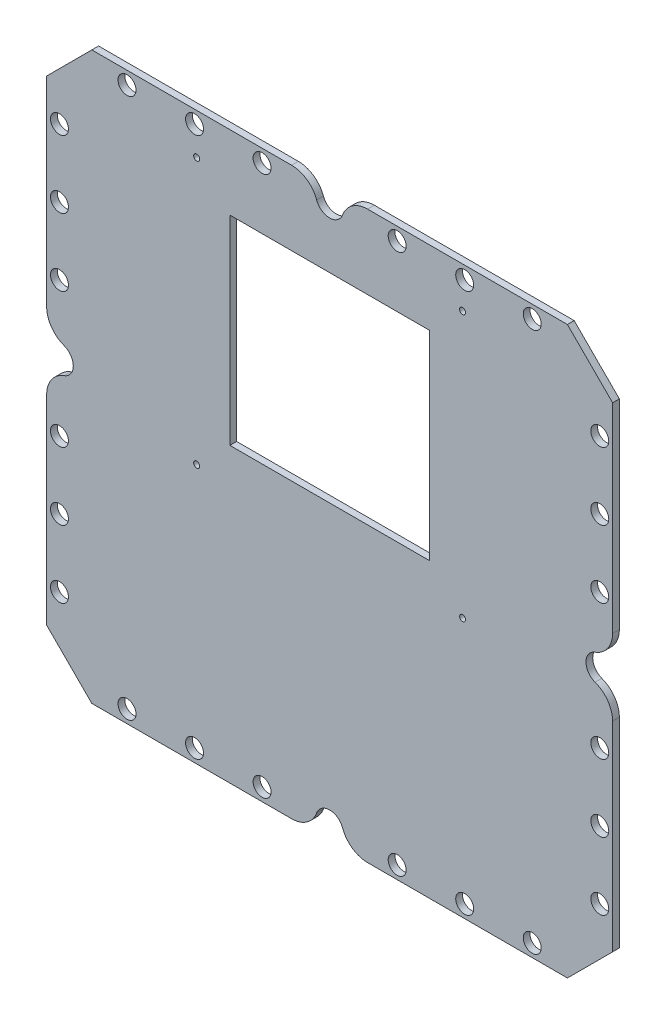
SolidWorks part; units mm, degrees
other "Markup1"
sketch "Sketch3" plane through (0, -212.852, 2.54) normal (0, 0, 1) x (1, 0, 0)
ref_plane "Front Plane" through (0, 0, 0) normal (0, 0, 1) x (1, 0, 0)
ref_plane "Top Plane" through (0, 0, 0) normal (0, 1, 0) x (1, 0, 0)
ref_plane "Right Plane" through (0, 0, 0) normal (1, 0, 0) x (0, 0, -1)
sketch "Sketch1" plane through (0, 0, 0) normal (0, 0, 1) x (1, 0, 0)
  line L0 (30.226, -4.826) -> (55.626, -4.826) construction
  line L1 (0, 0) -> (212.852, 0)
  line L2 (0, 0) -> (0, -212.852)
  line L3 (0, -212.852) -> (212.852, -212.852)
  line L4 (212.852, 0) -> (212.852, -212.852)
  line L5 (55.626, -4.826) -> (81.026, -4.826) construction
  line L6 (81.026, -4.826) -> (106.426, -4.826) construction
  line L7 (106.426, -4.826) -> (131.826, -4.826) construction
  line L8 (131.826, -4.826) -> (157.226, -4.826) construction
  line L9 (157.226, -4.826) -> (182.626, -4.826) construction
  line L10 (106.426, 0) -> (106.426, -212.852) construction
  line L11 (0, -106.426) -> (212.852, -106.426) construction
  line L12 (16.9978, 0) -> (0, -16.9978)
  line L13 (212.852, -16.9978) -> (195.8542, 0)
  line L14 (195.8542, -212.852) -> (212.852, -195.8542)
  line L15 (0, -195.8542) -> (16.9978, -212.852)
  line L16 (101.2317, 0) -> (101.2317, -4.826)
  line L17 (56.426, -15.3429) -> (156.426, -15.3429) construction
  line L18 (56.426, -15.3429) -> (56.426, -115.3429) construction
  line L19 (56.426, -115.3429) -> (156.426, -115.3429) construction
  line L20 (156.426, -15.3429) -> (156.426, -115.3429) construction
  line L21 (106.426, -115.3429) -> (106.426, -15.3429) construction
  line L22 (56.426, -65.3429) -> (156.426, -65.3429) construction
  line L23 (4.826, -111.6203) -> (0, -111.6203)
  line L24 (111.6203, -4.826) -> (111.6203, 0)
  line L25 (212.852, -101.2317) -> (208.026, -101.2317)
  line L26 (4.826, -101.2317) -> (0, -101.2317)
  line L27 (208.026, -111.6203) -> (212.852, -111.6203)
  line L28 (111.6203, -212.852) -> (111.6203, -208.026)
  line L30 (101.2317, -208.026) -> (101.2317, -212.852)
  line L35 (68.926, -27.8429) -> (143.926, -27.8429)
  line L36 (68.926, -27.8429) -> (68.926, -102.8429)
  line L37 (68.926, -102.8429) -> (143.926, -102.8429)
  line L38 (143.926, -27.8429) -> (143.926, -102.8429)
  line L39 (0, -111.6203) -> (4.826, -111.6203) [skipped]
  line L40 (4.826, -101.2317) -> (0, -101.2317) [skipped]
  circle A0 centre (30.226, -4.826) radius 3.38
  circle A1 centre (55.626, -4.826) radius 3.38
  circle A2 centre (81.026, -4.826) radius 3.38
  circle A3 centre (131.826, -4.826) radius 3.38
  circle A4 centre (157.226, -4.826) radius 3.38
  circle A5 centre (182.626, -4.826) radius 3.38
  circle A6 centre (106.426, -4.826) radius 5.1943
  circle A7 centre (208.026, -182.626) radius 3.38
  circle A8 centre (208.026, -157.226) radius 3.38
  circle A9 centre (208.026, -131.826) radius 3.38
  circle A10 centre (208.026, -106.426) radius 5.1943
  circle A11 centre (208.026, -81.026) radius 3.38
  circle A12 centre (208.026, -55.626) radius 3.38
  circle A13 centre (208.026, -30.226) radius 3.38
  circle A14 centre (30.226, -208.026) radius 3.38
  circle A15 centre (55.626, -208.026) radius 3.38
  circle A16 centre (81.026, -208.026) radius 3.38
  circle A17 centre (106.426, -208.026) radius 5.1943
  circle A18 centre (131.826, -208.026) radius 3.38
  circle A19 centre (157.226, -208.026) radius 3.38
  circle A20 centre (182.626, -208.026) radius 3.38
  circle A21 centre (4.826, -30.226) radius 3.38
  circle A22 centre (4.826, -55.626) radius 3.38
  circle A23 centre (4.826, -81.026) radius 3.38
  circle A24 centre (4.826, -106.426) radius 5.1943
  circle A25 centre (4.826, -131.826) radius 3.38
  circle A26 centre (4.826, -157.226) radius 3.38
  circle A27 centre (4.826, -182.626) radius 3.38
  circle A29 centre (56.426, -15.3429) radius 1.13
  circle A30 centre (156.426, -15.3429) radius 1.13
  circle A31 centre (156.426, -115.3429) radius 1.13
  circle A32 centre (56.426, -115.3429) radius 1.13
  circle A33 centre (46.426, -35.3429) radius 3.175
  circle A34 centre (106.426, -65.3429) radius 7.4189
  point P14 (106.426, -106.426)
  point P69 (106.426, -106.426)
  point P78 (106.426, -106.426)
  point P104 (106.426, -106.426)
  point P107 (106.426, -27.8429)
  point P108 (143.926, -65.3429)
  dimension "D1" = 6.76
  dimension "D5" = 10.3886
  dimension "D13" = 65.3429
  dimension "D14" = 2.26
  dimension "D19" = 6.35
  dimension "D2" = 30.226
  dimension "D3" = 25.4
  dimension "D4" = 4.826
  dimension "D6" = 212.852
  dimension "D7" = 212.852
  dimension "D9" = 45
  dimension "D10" = 24.0386
  dimension "D12" = 75
  dimension "D15" = 100
  dimension "D8" = 4
  dimension "D11" = 4
  dimension "D18" = 4
extrude "Boss-Extrude1" add sketch "Sketch1" along normal blind 2.54 contours A24 L2 L3 A17 L4 A10 L1 A6 A27 A26 A25 A23 A22 A21 A20 A19 A18 A16 A15 A14 A13 A12 A11 A9 A8 A7 A5 | A33 region at (106.4762, -112.6126, 0) region at (46.426, -35.3429, 0)
hole_wizard "#4-40 Tapped Hole1" positions "3DSketch1" profile "Sketch2" tap size "#4-40" standard "ANSI Inch" end condition through all
sketch3d "3DSketch1"
  line L0 (56.426, -15.3429, 2.54) -> (56.426, -15.3429, 0) construction
  line L1 (156.426, -15.3429, 2.54) -> (156.426, -15.3429, 0) construction
  line L2 (156.426, -115.3429, 2.54) -> (156.426, -115.3429, 0) construction
  line L3 (56.426, -115.3429, 2.54) -> (56.426, -115.3429, 0) construction
  point P0 (56.426, -15.3429, 2.54)
  point P4 (156.426, -15.3429, 2.54)
  point P8 (156.426, -115.3429, 2.54)
  point P12 (56.426, -115.3429, 2.54)
sketch "Sketch2" plane through (56.426, -15.3429, 2.54) normal (1, 0, 0) x (0, -1, 0)
  line L0 (0, 0) -> (0, 2.54)
  line L1 (0, 2.54) -> (1.1303, 2.54)
  line L2 (1.1303, 2.54) -> (1.1303, 0)
  line L5 (1.1303, 0) -> (0, 0)
  line L11 (0, -6.35) -> (0, 107.95) construction
  dimension "Thru Tap Drill Dia." = 2.2606
  dimension "Thru Tap Drill Depth" = 2.54
cosmetic thread "Hole Thread1" parameters "D2"=2.8448
cosmetic thread "Hole Thread2" parameters "D2"=2.8448
cosmetic thread "Hole Thread3" parameters "D2"=2.8448
cosmetic thread "Hole Thread4" parameters "D2"=2.8448
fillet "Fillet1" radius 10 8 edges at (101.2317, -212.852, 1.27) (111.6203, -212.852, 1.27) (212.852, -111.6203, 1.27) (212.852, -101.2317, 1.27) (111.6203, 0, 1.27) (101.2317, 0, 1.27) (0, -111.6203, 1.27) (0, -101.2317, 1.27)
